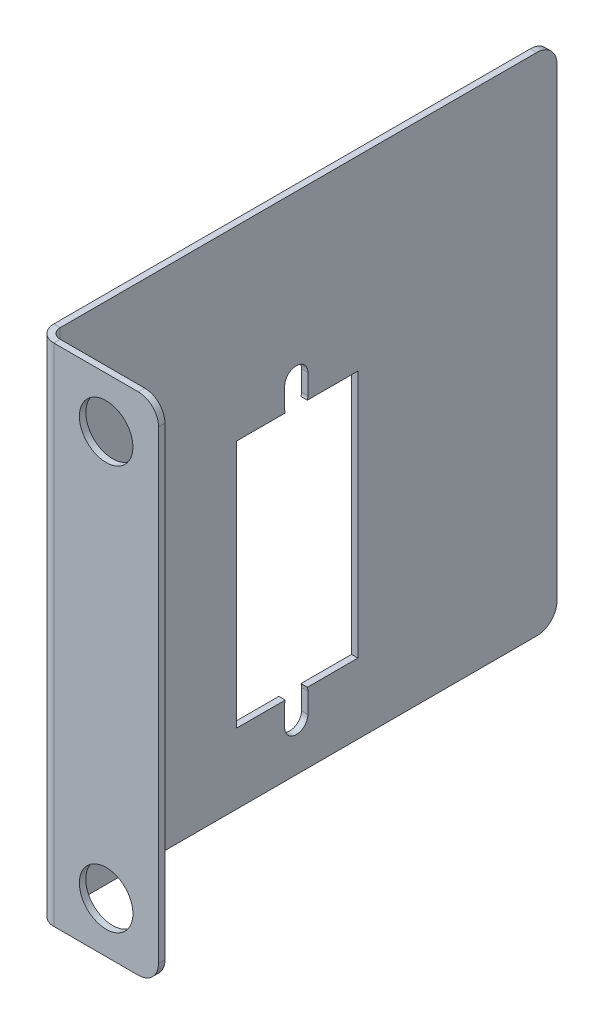
SolidWorks part; units mm, degrees
note: The reader was unsure of these and kept them because the rebuilt part matched: flange length of "Edge-Flange1".
ref_plane "Front Plane" through (0, 0, 0) normal (0, 0, 1) x (1, 0, 0)
ref_plane "Top Plane" through (0, 0, 0) normal (0, 1, 0) x (1, 0, 0)
ref_plane "Right Plane" through (0, 0, 0) normal (1, 0, 0) x (0, 0, -1)
sketch "Sketch1" plane through (0, 0, 0) normal (1, 0, 0) x (0, 0, -1)
  line L1 (-25.4, 25) -> (25.4, 25)
  line L2 (-25.4, 25) -> (-25.4, -25)
  line L3 (-25.4, -25) -> (25.4, -25)
  line L4 (25.4, 25) -> (25.4, -25)
  line L5 (-25.4, 25) -> (25.4, -25) construction
  line L6 (-25.4, -25) -> (25.4, 25) construction
  point P0 (0, 0)
  dimension "D1" = 50.8
  dimension "D2" = 50
base flange "Base-Flange1" sketch "Sketch1" thickness 0.635 reverse thickness direction no parameters "D1"=1
sketch "Sketch9" plane through (0, 0, 0) normal (1, 0, 0) x (0, 0, -1)
  line L0 (5.7, 6.55) -> (-6.3, 6.55)
  line L1 (-6.3, 5.5) -> (-6.3, -17) construction
  line L2 (5.7, -18.05) -> (-6.3, -18.05)
  line L4 (-6.3, -18.05) -> (-6.3, 6.55)
  line L5 (5.7, -18.05) -> (5.7, 6.55)
  point P0 (-6.3, -5.75)
  point P3 (-0.4, 5.5)
  point P6 (-6.3, -5.75)
  dimension "D1" = 12
  dimension "D2" = 24.6
extrude "Cut-Extrude1" cut sketch "Sketch9" against normal through all normal cut yes
sketch "Sketch10" plane through (-0.635, 0, 0) normal (-1, 0, 0) x (0, 0, 1)
  line L0 (0.4, -20.4) -> (0.4, -18.4) construction
  line L3 (-0.75, -20.4) -> (-0.75, -18.4)
  line L6 (1.55, -20.4) -> (1.55, -18.4)
  line L8 (0.4, 6.9) -> (0.4, 8.9) construction
  line L9 (-0.75, 6.9) -> (-0.75, 8.9)
  line L10 (1.55, 6.9) -> (1.55, 8.9)
  arc A4 (-0.75, -20.4) -> (1.55, -20.4) centre (0.4, -20.4) ccw
  arc A5 (1.55, -18.4) -> (-0.75, -18.4) centre (0.4, -18.4) ccw
  arc A6 (-0.75, 6.9) -> (1.55, 6.9) centre (0.4, 6.9) ccw
  arc A7 (1.55, 8.9) -> (-0.75, 8.9) centre (0.4, 8.9) ccw
  point P0 (0.4, -19.4)
  point P1 (0.4, 7.9)
  point P4 (0.4, -19.4)
  point P11 (0.4, 7.9)
  point P16 (0.4, 7.9)
  point P17 (0.4, -19.4)
  dimension "D2" = 2.3
  dimension "D1" = 2
  dimension "D3" = 2.3
  dimension "D4" = 2
extrude "Cut-Extrude2" cut sketch "Sketch10" against normal through all normal cut yes
edge flange "Edge-Flange1" sketch "Sketch13" flange angle 90 flange length 12 flange position material inside bend radius 1 thickness 0.635 relief rectangular parameters "D6"=10
sketch "Sketch13" plane through (0, 0, 25.4) normal (0, 0, 1) x (0, -1, 0)
  line L0 (-25, 0) -> (25, 0) construction
  line L1 (-25, 0) -> (25, 0)
  line L2 (-25, 0) -> (-25, 11.365)
  line L3 (-25, 11.365) -> (25, 11.365)
  line L4 (25, 11.365) -> (25, 0)
bend "EdgeBend1" bend radius 1 bend angle 90 parameters "D5"=1
sketch "Sketch14" plane through (0, 0, 24.765) normal (0, 0, -1) x (-1, 0, 0)
  line L0 (-6.1825, 25) -> (-6.1825, -25) construction
  line L4 (-11.365, 25) -> (-1, 25) construction
  line L5 (-1, -25) -> (-11.365, -25) construction
  circle A0 centre (-6.1825, -20) radius 2.65
  circle A3 centre (-6.1825, 20) radius 2.65
  point P11 (-6.1825, 25)
  dimension "D3" = 5.3
  dimension "D2" = 5.3
  dimension "D1" = 20
  dimension "D4" = 20
extrude "Cut-Extrude3" cut sketch "Sketch14" against normal through all normal cut yes
fillet "Fillet1" radius 2 4 edges at (11.365, 25, 25.0825) (11.365, -25, 25.0825) (-0.3175, -25, -25.4) (-0.3175, 25, -25.4)
sketch "Bend-Lines1" [suppressed] plane through (0, 0, 0) normal (0, 1, 0) x (1, 0, 0)
sketch "Bounding-Box1" [suppressed] plane through (0, 0, 0) normal (0, 1, 0) x (1, 0, 0)
other "Bend-Notch1" [suppressed] parameters "D1"=0, "D3"=5, "D2"=3
sheet metal parameters "Sheet-Metal1" thickness 0.635 parameters "D1"=1
flat pattern "Flat-Pattern1" [suppressed]
sketch "Bend-Lines2" plane through (0, 0, 0) normal (0, 1, 0) x (1, 0, 0)
sketch3d "Bounding-Box2" [suppressed]
  line L0 (25.4, -20, 0) -> (-25.4, -20, 0) construction
  line L1 (25.4, 20, 0) -> (-25.4, 20, 0) construction
  line L2 (25.4, -20, 0) -> (25.4, 20, 0) construction
  line L3 (-25.4, -20, 0) -> (-25.4, 20, 0) construction
sheet metal parameters "Sheet-Metal3" thickness 0.635 parameters "D1"=1
flat pattern "Flat-Pattern1"
sketch "Bend-Lines2" plane through (0, 0, 0) normal (1, 0, 0) x (0, 0, -1)
  line L0 (-25.4, -19.3998) -> (25.4, -19.3998) construction
  line L1 (-25.4, -19.3998) -> (25.4, -19.3998) construction
sketch3d "Bounding-Box2" [suppressed]
  line L0 (-25.4, -30.7995, 0) -> (25.4, -30.7995, 0) construction
  line L1 (-25.4, 20, 0) -> (25.4, 20, 0) construction
  line L2 (-25.4, -30.7995, 0) -> (-25.4, 20, 0) construction
  line L3 (25.4, -30.7995, 0) -> (25.4, 20, 0) construction
sheet metal parameters "Sheet-Metal4" thickness 0.635 parameters "D1"=1
flat pattern "Flat-Pattern1"
sketch "Bend-Lines2" plane through (0, 0, 0) normal (1, 0, 0) x (0, 0, -1)
sketch3d "Bounding-Box2" [suppressed]
  line L0 (-30, -15, 0) -> (30, -15, 0) construction
  line L1 (-30, 15, 0) -> (30, 15, 0) construction
  line L2 (-30, -15, 0) -> (-30, 15, 0) construction
  line L3 (30, -15, 0) -> (30, 15, 0) construction
sheet metal parameters "Sheet-Metal6" thickness 0.635 parameters "D1"=1
flat pattern "Flat-Pattern1"
sketch "Bend-Lines2" plane through (0, 0, 0) normal (1, 0, 0) x (0, 0, -1)
  line L0 (-29.3998, 15) -> (-29.3998, -15) construction
  line L1 (-29.3998, 15) -> (-29.3998, -15) construction
sketch3d "Bounding-Box2" [suppressed]
  line L0 (-40.7995, -15, 0) -> (30, -15, 0) construction
  line L1 (-40.7995, 15, 0) -> (30, 15, 0) construction
  line L2 (-40.7995, -15, 0) -> (-40.7995, 15, 0) construction
  line L3 (30, -15, 0) -> (30, 15, 0) construction
bend of the flat pattern "Flatten-<EdgeBend1>1"
sheet metal parameters "Sheet-Metal7" thickness 0.635 parameters "D1"=1
flat pattern "Flat-Pattern1"
sketch "Bend-Lines2" plane through (0, 0, 0) normal (1, 0, 0) x (0, 0, -1)
  line L0 (-24.7998, 25) -> (-24.7998, -25) construction
  line L1 (-24.7998, 25) -> (-24.7998, -25) construction
sketch3d "Bounding-Box2" [suppressed]
  line L0 (-36.1995, 25, 0) -> (25.4, 25, 0) construction
  line L1 (-36.1995, -25, 0) -> (25.4, -25, 0) construction
  line L2 (-36.1995, 25, 0) -> (-36.1995, -25, 0) construction
  line L3 (25.4, 25, 0) -> (25.4, -25, 0) construction
bend of the flat pattern "Flatten-<EdgeBend1>1"
